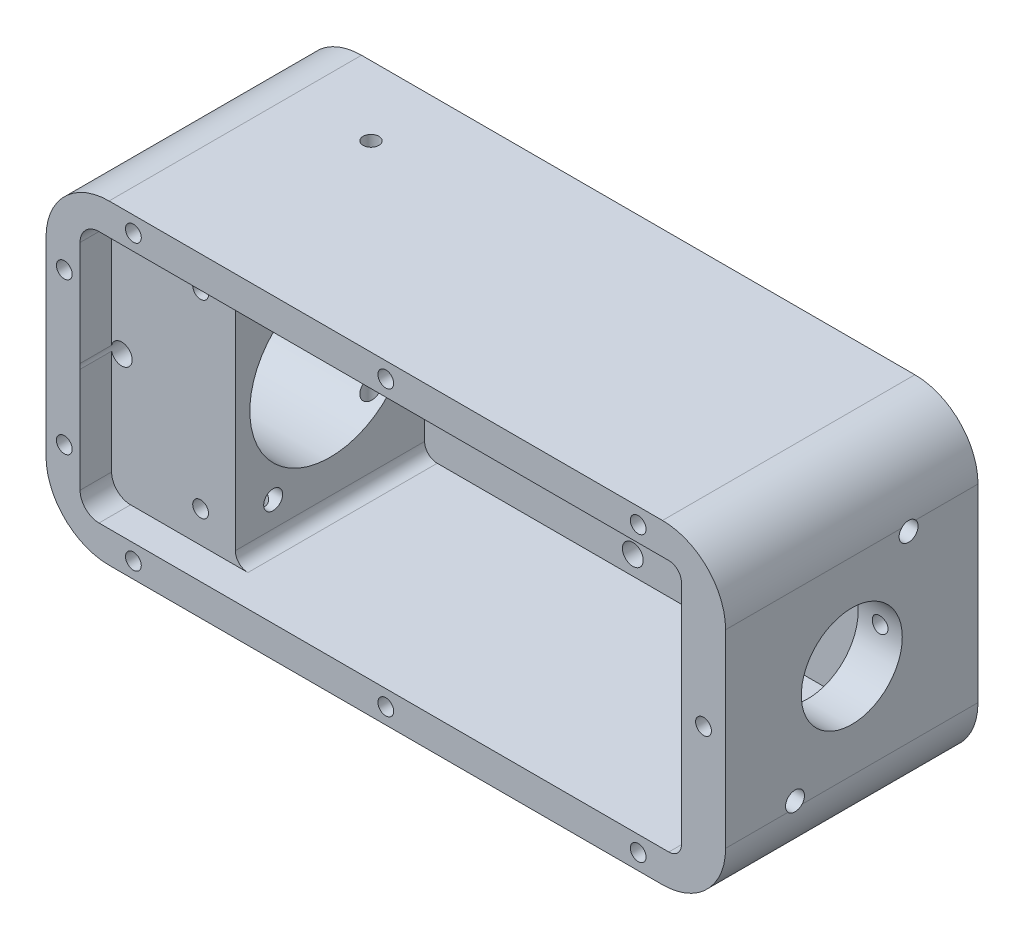
SolidWorks part; units mm, degrees
ref_plane "Front Plane" through (0, 0, 0) normal (0, 0, 1) x (1, 0, 0)
ref_plane "Top Plane" through (0, 0, 0) normal (0, 1, 0) x (1, 0, 0)
ref_plane "Right Plane" through (0, 0, 0) normal (1, 0, 0) x (0, 0, -1)
ref_plane "Plane1" through (0, 0, 40) normal (0, 0, 1) x (1, 0, 0)
sketch "Sketch1" plane through (0, 0, 40) normal (0, 0, 1) x (1, 0, 0)
  line L0 (0, 0) -> (0, -50)
  line L1 (0, -50) -> (107.7, -50)
  line L2 (107.7, -50) -> (107.7, 0)
  line L3 (107.7, 0) -> (0, 0)
extrude "Boss-Extrude1" add sketch "Sketch1" against normal blind 40
sketch "Sketch2" plane through (0, 0, 40) normal (0, 0, 1) x (1, 0, 0)
  line L0 (100.7, -5) -> (25, -5)
  line L1 (25, -5) -> (25, -45)
  line L2 (25, -45) -> (100.7, -45)
  line L3 (100.7, -45) -> (100.7, -5)
extrude "Cut-Extrude1" cut sketch "Sketch2" against normal blind 35
ref_plane "Plane2" through (0, 0, 35) normal (0, 0, -1) x (-1, 0, 0)
sketch "Sketch4" plane through (0, 0, 35) normal (0, 0, -1) x (-1, 0, 0)
  line L0 (-5.4, -45) -> (-5.4, -5)
  line L1 (-5.4, -5) -> (-25, -5)
  line L2 (-25, -5) -> (-25, -45)
  line L3 (-25, -45) -> (-5.4, -45)
extrude "Cut-Extrude2" cut sketch "Sketch4" against normal up to surface up to plane "Plane1"
sketch "Sketch5" plane through (0, 0, 0) normal (0, 0, -1) x (-1, 0, 0)
  line L0 (-99.7, -19.85) -> (-99.7, -30.15)
  line L1 (-99.7, -30.15) -> (-54.7, -30.15)
  line L2 (-54.7, -30.15) -> (-54.7, -19.85)
  line L3 (-54.7, -19.85) -> (-99.7, -19.85)
extrude "Cut-Extrude3" cut sketch "Sketch5" against normal through all
hole_wizard "#4 Clearance Hole1" positions "Sketch7" profile "Sketch6" hole size "#4" standard "ANSI Inch"
sketch "Sketch7" plane through (0, 0, 0) normal (0, 0, -1) x (-1, 0, 0)
  point P0 (-58, -42)
  point P1 (-78, -42)
  point P2 (-98, -42)
  point P3 (-98, -8)
  point P4 (-58, -8)
  point P5 (-78, -8)
sketch "Sketch6" plane through (58, -42, 0) normal (1, 0, 0) x (0, 1, 0)
  line L0 (0, 0) -> (0, 40)
  line L1 (0, 40) -> (1.65, 40)
  line L2 (1.65, 40) -> (1.65, 0)
  line L5 (1.65, 0) -> (0, 0)
  line L11 (0, -6.35) -> (0, 107.95) construction
  dimension "Thru Hole Dia." = 3.3
  dimension "Thru Hole Depth" = 40
hole_wizard "#4 Clearance Hole2" positions "Sketch9" profile "Sketch8" hole size "#4" standard "ANSI Inch"
sketch "Sketch9" plane through (0, 0, 0) normal (0, 0, -1) x (-1, 0, 0)
  point P0 (-8, -8)
sketch "Sketch8" plane through (8, -8, 0) normal (1, 0, 0) x (0, 1, 0)
  line L0 (0, 0) -> (0, 10)
  line L1 (0, 10) -> (1.65, 10)
  line L2 (1.65, 10) -> (1.65, 0)
  line L5 (1.65, 0) -> (0, 0)
  line L10 (0, 10) -> (-1.65, 10) construction
  line L11 (0, -6.35) -> (0, 107.95) construction
  dimension "Hole Dia." = 3.3
  dimension "Hole Depth" = 10
  dimension "Drill Angle" = 180
hole_wizard "#3 Clearance Hole1" positions "Sketch11" profile "Sketch10" hole size "#3" standard "ANSI Inch"
sketch "Sketch11" plane through (107.7, 0, 0) normal (1, 0, 0) x (0, 0, -1)
  point P0 (-29, -39)
sketch "Sketch10" plane through (107.7, -39, 29) normal (0, 1, 0) x (0, 0, -1)
  line L0 (0, 0) -> (0, 7)
  line L1 (0, 7) -> (1.5, 7)
  line L2 (1.5, 7) -> (1.5, 0)
  line L5 (1.5, 0) -> (0, 0)
  line L11 (0, -6.35) -> (0, 107.95) construction
  dimension "Thru Hole Dia." = 3
  dimension "Thru Hole Depth" = 7
hole_wizard "#3 Clearance Hole2" positions "Sketch13" profile "Sketch12" hole size "#3" standard "ANSI Inch"
sketch "Sketch13" plane through (100.7, 0, 0) normal (-1, 0, 0) x (0, 0, 1)
  point P0 (11, -11)
sketch "Sketch12" plane through (100.7, -11, 11) normal (0, 1, 0) x (0, 0, 1)
  line L0 (0, 0) -> (0, 7)
  line L1 (0, 7) -> (1.5, 7)
  line L2 (1.5, 7) -> (1.5, 0)
  line L5 (1.5, 0) -> (0, 0)
  line L11 (0, -6.35) -> (0, 107.95) construction
  dimension "Thru Hole Dia." = 3
  dimension "Thru Hole Depth" = 7
hole_wizard "#2 Clearance Hole1" positions "Sketch15" profile "Sketch14" hole size "#2" standard "ANSI Inch"
sketch "Sketch15" plane through (0, 0, 0) normal (0, 1, 0) x (1, 0, 0)
  point P0 (22.5, -11)
sketch "Sketch14" plane through (22.5, 0, 11) normal (1, 0, 0) x (0, 0, 1)
  line L0 (0, 0) -> (0, 50)
  line L1 (0, 50) -> (1.25, 50)
  line L2 (1.25, 50) -> (1.25, 0)
  line L5 (1.25, 0) -> (0, 0)
  line L11 (0, -6.35) -> (0, 107.95) construction
  dimension "Thru Hole Dia." = 2.5
  dimension "Thru Hole Depth" = 50
hole_wizard "Hole1" positions "Sketch17" profile "Sketch16" legacy
sketch "Sketch17" plane through (107.7, 0, 0) normal (1, 0, 0) x (0, 0, -1)
  point P0 (-20, -25)
sketch "Sketch16" plane through (107.7, -25, 20) normal (0, 1, 0) x (0, 0, -1)
  line L0 (0, 0) -> (0, 7)
  line L1 (0, 7) -> (8, 7)
  line L2 (8, 7) -> (8, 0)
  line L3 (8, 0) -> (0, 0)
  line L4 (0, 110) -> (0, -10) construction
  dimension "Diameter" = 16
  dimension "Depth" = 7
hole_wizard "#2 Clearance Hole2" positions "Sketch19" profile "Sketch18" hole size "#2" standard "ANSI Inch"
sketch "Sketch19" plane through (0, 0, 40) normal (0, 0, 1) x (1, 0, 0)
  point P0 (104.2, -25)
sketch "Sketch18" plane through (104.2, -25, 40) normal (1, 0, 0) x (0, -1, 0)
  line L0 (0, 0) -> (0, 52.0983)
  line L1 (0, 52.0983) -> (1.25, 52.0983)
  line L2 (1.25, 52.0983) -> (1.25, 0)
  line L5 (1.25, 0) -> (0, 0)
  line L10 (0, 52.0983) -> (-1.25, 52.0983) construction
  line L11 (0, -6.35) -> (0, 107.95) construction
  dimension "Hole Dia." = 2.5
  dimension "Hole Depth" = 52.0983
  dimension "Drill Angle" = 180
hole_wizard "#3 Clearance Hole3" positions "Sketch21" profile "Sketch20" hole size "#3" standard "ANSI Inch"
sketch "Sketch21" plane through (0, 0, 0) normal (-1, 0, 0) x (0, 0, 1)
  point P0 (29, -39)
  point P1 (11, -11)
sketch "Sketch20" plane through (0, -39, 29) normal (0, 1, 0) x (0, 0, 1)
  line L0 (0, 0) -> (0, 107.7)
  line L1 (0, 107.7) -> (1.5, 107.7)
  line L2 (1.5, 107.7) -> (1.5, 0)
  line L5 (1.5, 0) -> (0, 0)
  line L11 (0, -6.35) -> (0, 107.95) construction
  dimension "Thru Hole Dia." = 3
  dimension "Thru Hole Depth" = 107.7
hole_wizard "#2 Clearance Hole3" positions "Sketch23" profile "Sketch22" hole size "#2" standard "ANSI Inch"
sketch "Sketch23" plane through (0, 0, 40) normal (0, 0, 1) x (1, 0, 0)
  point P0 (2.9, -37)
  point P1 (93.85, -2.5)
  point P2 (53.85, -2.5)
  point P3 (13.85, -2.5)
  point P4 (2.9, -13)
  point P5 (13.85, -47.5)
  point P6 (53.85, -47.5)
  point P7 (93.85, -47.5)
sketch "Sketch22" plane through (2.9, -37, 40) normal (1, 0, 0) x (0, -1, 0)
  line L0 (0, 0) -> (0, 10)
  line L1 (0, 10) -> (1.25, 10)
  line L2 (1.25, 10) -> (1.25, 0)
  line L5 (1.25, 0) -> (0, 0)
  line L10 (0, 10) -> (-1.25, 10) construction
  line L11 (0, -6.35) -> (0, 107.95) construction
  dimension "Hole Dia." = 2.5
  dimension "Hole Depth" = 10
  dimension "Drill Angle" = 180
hole_wizard "#2 Clearance Hole4" positions "Sketch25" profile "Sketch24" hole size "#2" standard "ANSI Inch"
sketch "Sketch25" plane through (0, -50, 0) normal (0, -1, 0) x (-1, 0, 0)
  point P0 (-22.5, -29)
sketch "Sketch24" plane through (22.5, -50, 29) normal (1, 0, 0) x (0, 0, -1)
  line L0 (0, 0) -> (0, 9.5)
  line L1 (0, 9.5) -> (1.25, 9.5)
  line L2 (1.25, 9.5) -> (1.25, 0)
  line L5 (1.25, 0) -> (0, 0)
  line L11 (0, -6.35) -> (0, 107.95) construction
  dimension "Thru Hole Dia." = 2.5
  dimension "Thru Hole Depth" = 9.5
hole_wizard "1 (1) Diameter Hole1" positions "Sketch27" profile "Sketch26" hole size "1" standard "ANSI Inch"
sketch "Sketch27" plane through (25, 0, 0) normal (1, 0, 0) x (0, 0, -1)
  point P0 (-20, -25)
sketch "Sketch26" plane through (25, -25, 20) normal (0, 1, 0) x (0, 0, -1)
  line L0 (0, 0) -> (0, 25)
  line L1 (0, 25) -> (12.7, 25)
  line L2 (12.7, 25) -> (12.7, 0)
  line L5 (12.7, 0) -> (0, 0)
  line L11 (0, -6.35) -> (0, 107.95) construction
  dimension "Thru Hole Dia." = 25.4
  dimension "Thru Hole Depth" = 25
ref_plane "Plane3" through (0, 0, 32.5924) normal (0, 0, -1) x (-1, 0, 0)
hole_wizard "#4 Clearance Hole3" positions "Sketch29" profile "Sketch28" hole size "#4" standard "ANSI Inch"
sketch "Sketch29" plane through (0, 0, 32.5924) normal (0, 0, -1) x (-1, 0, 0)
  point P0 (-7, -25)
sketch "Sketch28" plane through (7, -25, 32.5924) normal (1, 0, 0) x (0, 1, 0)
  line L0 (0, 0) -> (0, 40)
  line L1 (0, 40) -> (1.65, 40)
  line L2 (1.65, 40) -> (1.65, 0)
  line L5 (1.65, 0) -> (0, 0)
  line L10 (0, 40) -> (-1.65, 40) construction
  line L11 (0, -6.35) -> (0, 107.95) construction
  dimension "Hole Dia." = 3.3
  dimension "Hole Depth" = 40
  dimension "Drill Angle" = 180
hole_wizard "#2 Clearance Hole5" positions "Sketch31" profile "Sketch30" hole size "#2" standard "ANSI Inch"
sketch "Sketch31" plane through (0, 0, 35) normal (0, 0, 1) x (1, 0, 0)
  point P0 (19.5, -10)
  point P1 (19.5, -40)
sketch "Sketch30" plane through (19.5, -10, 35) normal (1, 0, 0) x (0, -1, 0)
  line L0 (0, 0) -> (0, 10)
  line L1 (0, 10) -> (1.25, 10)
  line L2 (1.25, 10) -> (1.25, 0)
  line L5 (1.25, 0) -> (0, 0)
  line L10 (0, 10) -> (-1.25, 10) construction
  line L11 (0, -6.35) -> (0, 107.95) construction
  dimension "Hole Dia." = 2.5
  dimension "Hole Depth" = 10
  dimension "Drill Angle" = 180
fillet "Fillet1" radius 2 8 edges at (54.7, -19.85, 2.5) (54.7, -30.15, 2.5) (25, -45, 20) (100.7, -5, 22.5) (99.7, -30.15, 2.5) (100.7, -45, 22.5) (25, -5, 20) (99.7, -19.85, 2.5) tangent propagation no
fillet "Fillet2" radius 3 2 edges at (5.4, -5, 37.5) (5.4, -45, 37.5) tangent propagation no
fillet "Fillet3" radius 10 4 edges at (107.7, 0, 20) (107.7, -50, 20) (0, 0, 20) (0, -50, 20) tangent propagation no
